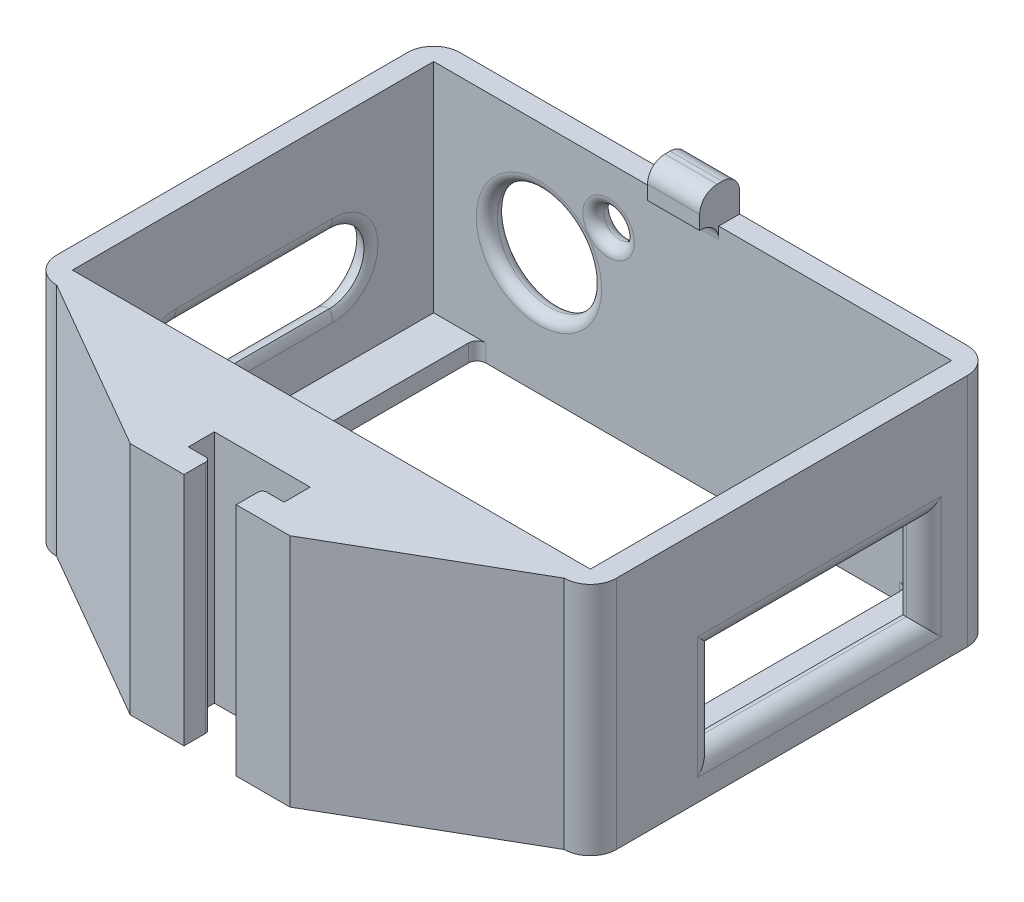
SolidWorks part; units mm, degrees
ref_plane "Спереди" through (0, 0, 0) normal (0, 0, 1) x (1, 0, 0)
ref_plane "Сверху" through (0, 0, 0) normal (0, 1, 0) x (1, 0, 0)
ref_plane "Справа" through (0, 0, 0) normal (1, 0, 0) x (0, 0, -1)
other "Configuration Table"
sketch "Эскиз1" plane through (0, 0, 0) normal (0, 1, 0) x (1, 0, 0)
  line L0 (-2.4, 43.9) -> (61.9, 43.9)
  line L1 (0, 0) -> (59.5, 0)
  line L2 (0, 0) -> (0, 41.5)
  line L3 (0, 41.5) -> (59.5, 41.5)
  line L4 (59.5, 0) -> (59.5, 41.5)
  line L5 (61.9, -2.4) -> (61.9, 43.9)
  line L6 (-2.4, -2.4) -> (61.9, -2.4)
  line L7 (-2.4, -2.4) -> (-2.4, 43.9)
  line L12 (5, 41.5) -> (5, 0)
  line L16 (54.5, 41.5) -> (54.5, 0)
  dimension "D1" = 59.5
  dimension "D2" = 41.5
  dimension "D4" = 5
  dimension "D5" = 5
  dimension "D6" = 41.5
  dimension "D7" = 41.5
  dimension "D3" = 2.4
extrude "Бобышка-Вытянуть2" add sketch "Эскиз1" along normal blind 27 contours L7 L6 L5 L0 L4 L1 L2 L3 region at (29.75, 0, -43.1077)
extrude "Бобышка-Вытянуть3" add sketch "Эскиз1<3>" along normal blind 2 contours L12 L3 L2 L1 | L3 L16 L1 L4 region at (2.5, 0, -20.75) region at (57, 0, -20.75)
sketch "Эскиз1<3>" plane through (0, 0, 0) normal (0, 1, 0) x (1, 0, 0) same geometry as "Эскиз1"
fillet "Скругление1" radius 3 4 edges at (-2.4, 13.5, -43.9) (61.9, 13.5, -43.9) (61.9, 13.5, 2.4) (-2.4, 13.5, 2.4)
fillet "Скругление2" radius 1 4 edges at (54.5, 1, 0) (5, 1, 0) (5, 1, -41.5) (54.5, 1, -41.5)
sketch "Эскиз2" plane through (0, 0, -43.9) normal (0, 0, -1) x (-1, 0, 0)
  line L0 (2.4, 27) -> (2.4, 0) construction
  line L4 (-58.9, 0) -> (-0.6, 0)
  line L5 (-0.6, 0) -> (-0.6, 27)
  line L6 (-0.6, 27) -> (-58.9, 27)
  line L7 (-58.9, 27) -> (-58.9, 0)
  line L8 (-58.9, 0) -> (-0.6, 0)
  line L9 (-0.6, 0) -> (-0.6, 27)
  line L10 (-0.6, 27) -> (-58.9, 27)
  line L11 (-58.9, 27) -> (-58.9, 0)
  circle A0 centre (-12.1, 14) radius 6
  circle A1 centre (-20.1, 20.5) radius 1.75
  dimension "D1" = 0
  dimension "D3" = 12
  dimension "D5" = 22.5
  dimension "D6" = 3.5
  dimension "D2" = 14.5
  dimension "D4" = 13
  dimension "D7" = 6.5
extrude "Вырез-Вытянуть2" cut sketch "Эскиз2" against normal blind 8 contours A0 | A1
sketch "Эскиз4" plane through (61.9, 0, 0) normal (1, 0, 0) x (0, 0, -1)
  line L0 (43.9, 27) -> (43.9, 0) construction
  line L1 (11.9, 14.5) -> (35.9, 14.5)
  line L2 (11.9, 14.5) -> (11.9, 4.5)
  line L3 (11.9, 4.5) -> (35.9, 4.5)
  line L4 (0.6, 0) -> (40.9, 0)
  line L5 (40.9, 0) -> (40.9, 27)
  line L6 (40.9, 27) -> (0.6, 27)
  line L7 (0.6, 27) -> (0.6, 0)
  line L8 (0.6, 0) -> (40.9, 0)
  line L9 (40.9, 0) -> (40.9, 27)
  line L10 (40.9, 27) -> (0.6, 27)
  line L11 (0.6, 27) -> (0.6, 0)
  line L12 (35.9, 14.5) -> (35.9, 4.5)
  dimension "D2" = 10
  dimension "D3" = 24
  dimension "D4" = 8
  dimension "D5" = 4.5
  dimension "D1" = 0
extrude "Вырез-Вытянуть4" cut sketch "Эскиз4" against normal blind 12 contours L2 L3 L12 L1
fillet "Скругление5" radius 2 4 edges at (61.9, 4.5, -23.9) (61.9, 9.5, -35.9) (61.9, 9.5, -11.9) (61.9, 14.5, -23.9)
sketch "Эскиз10" plane through (-2.4, 0, 0) normal (-1, 0, 0) x (0, 0, 1)
  line L0 (-29.9, 12) -> (-11.9, 12) construction
  line L1 (-29.9, 16) -> (-11.9, 16)
  line L2 (-29.9, 8) -> (-11.9, 8)
  line L3 (-0.6, 0) -> (-40.9, 0) construction
  line L5 (-43.9, 0) -> (-43.9, 27) construction
  arc A0 (-29.9, 16) -> (-29.9, 8) centre (-29.9, 12) ccw
  arc A1 (-11.9, 8) -> (-11.9, 16) centre (-11.9, 12) ccw
  point P2 (-20.9, 12)
  dimension "D3" = 8
  dimension "D1" = 18
  dimension "D2" = 8
  dimension "D4" = 23
extrude "Вырез-Вытянуть5" cut sketch "Эскиз10" against normal blind 12 contours L1 A1 L2 A0
fillet "Скругление6" radius 2 4 edges at (-2.4, 8, -20.9) (-2.4, 12, -33.9) (-2.4, 16, -20.9) (-2.4, 12, -7.9)
fillet "Скругление7" radius 2 4 edges at (0, 8, -20.9) (0, 12, -33.9) (0, 16, -20.9) (0, 12, -7.9)
fillet "Скругление16" radius 1.2 4 edges at (18.35, 20.5, -41.5) (18.35, 20.5, -43.9) (6.1, 14, -41.5) (6.1, 14, -43.9)
ref_plane "Плоскость1" through (29.75, 0, 0) normal (1, 0, 0) x (0, 0, -1)
sketch "Эскиз16" plane through (29.75, 0, 0) normal (1, 0, 0) x (0, 0, -1)
  line L0 (43.9, 29.2618) -> (43.9, 24.6269)
  line L2 (43.9, 27) -> (43.9, 29.2618)
  line L3 (41.9, 31.2618) -> (41.3153, 31.2618)
  line L4 (43.9, 27) -> (40.9, 27)
  line L5 (43.9, 0) -> (43.9, 27)
  line L6 (40.9, 0) -> (43.9, 0)
  line L7 (40.9, 27) -> (40.9, 0)
  line L9 (43.9, 0) -> (43.9, 27)
  line L10 (40.9, 0) -> (43.9, 0)
  line L12 (0, 27) -> (0, 2)
  line L13 (0, 2) -> (41.5, 2)
  line L14 (41.5, 2) -> (41.5, 27)
  line L15 (41.5, 27) -> (0, 27)
  line L16 (0, 27) -> (0, 2)
  line L17 (0, 2) -> (41.5, 2)
  line L20 (39.3153, 29.2618) -> (39.3153, 27.6498)
  line L21 (39.3153, 27.6498) -> (39.5, 27.6498)
  line L22 (41.5, 25.6498) -> (41.5, 24.6269)
  line L23 (41.5, 24.6269) -> (43.9, 24.6269)
  arc A0 (41.9, 31.2618) -> (43.9, 29.2618) centre (41.9, 29.2618) cw
  arc A1 (41.3153, 31.2618) -> (39.3153, 29.2618) centre (41.3153, 29.2618) ccw
  arc A2 (41.5, 25.6498) -> (39.5, 27.6498) centre (39.5, 25.6498) ccw
  dimension "D2" = 0
  dimension "D3" = 2
  dimension "D1" = 0
extrude "Бобышка-Вытянуть9" add sketch "Эскиз16" along normal mid plane 6 contours A0 L3 A1 L20 L21 A2 L22 L23 L0
sketch "Эскиз17" plane through (0, 27, 0) normal (0, 1, 0) x (1, 0, 0)
  line L0 (0.6, -2.4) -> (58.9, -2.4) construction
  line L1 (0.6, -2.4) -> (58.9, -2.4)
  line L2 (0.6, -2.4) -> (20.5772, -13.9338)
  line L3 (54.9, -2.4) -> (38.3869, -11.9338)
  line L4 (4.6, -2.4) -> (21.1131, -11.9338)
  line L5 (29.75, -2.4) -> (29.75, -13.9338)
  line L6 (8.0641, -4.4) -> (30.7742, -17.5117) construction
  line L7 (8.0641, -4.4) -> (58.9, -4.4) construction
  line L8 (58.9, -2.4) -> (38.9228, -13.9338)
  line L9 (29.75, -13.9338) -> (20.5772, -13.9338)
  line L10 (29.75, -11.9338) -> (21.1131, -11.9338)
  line L11 (42.4354, -13.9338) -> (17.1131, -13.9338) construction
  line L12 (0.6, -2.4) -> (29.7742, -19.2437) construction
  line L13 (42.4354, -11.9338) -> (17.1131, -11.9338) construction
  line L14 (29.75, -11.9338) -> (38.3869, -11.9338)
  line L15 (29.75, -13.9338) -> (38.9228, -13.9338)
  line L16 (-2.4, 0.6) -> (-2.4, 40.9) construction
  point P25 (38.3869, -11.9338)
  point P28 (21.1131, -11.9338)
  line M26 (0.6, -2.4) -> (58.9, -2.4)
  dimension "D1" = 30
  dimension "D4" = 2
  dimension "D2" = 2
extrude "Бобышка-Вытянуть11" add sketch "Эскиз17" against normal up to vertex (27 mm away) contours L5 L14 L3 M26 | L10 L5 L1 L4 | L5 L15 L8 L1 L3 L14 | L5 L10 L4 L2 L9 M26 region at (15.7301, 27, 9.2458) region at (20.6307, 27, 6.3903) region at (38.8693, 27, 6.3903) region at (43.7699, 27, 9.2458) up to point (58.9, 0, 2.4)
sketch "Эскиз19" plane through (0, 27, 0) normal (0, 1, 0) x (1, 0, 0)
  line L0 (20.5772, -13.9338) -> (38.9228, -13.9338) construction
  line L1 (0, 0) -> (59.5, 0) construction
  line L2 (20.5772, -13.9338) -> (38.9228, -13.9338) construction
  line L3 (0, 0) -> (59.5, 0)
  line L4 (29.75, 0) -> (29.75, -13.9338) construction
  line L5 (26.75, -13.9338) -> (32.75, -13.9338)
  line L6 (32.75, -13.9338) -> (32.75, -10.9338)
  line L7 (32.75, -10.9338) -> (35.25, -10.9338)
  line L8 (35.25, -10.9338) -> (35.25, -7.9338)
  line L9 (35.25, -7.9338) -> (24.25, -7.9338)
  line L10 (29.75, -7.9338) -> (29.75, -13.9338)
  line L11 (24.25, -10.9338) -> (24.25, -7.9338)
  line L12 (26.75, -10.9338) -> (24.25, -10.9338)
  line L13 (26.75, -13.9338) -> (26.75, -10.9338)
  line M24 (20.5772, -13.9338) -> (38.9228, -13.9338)
  dimension "D1" = 3
  dimension "D2" = 3
  dimension "D3" = 3
  dimension "D4" = 2.5
extrude "Вырез-Вытянуть6" cut sketch "Эскиз19" against normal through all contours L13 L10 L9 L11 L12 M24 | L9 L10 L5 L6 L7 L8 region at (27.4412, 27, 10.4927) region at (32.0588, 27, 10.4927)
fillet "Скругление17" radius 0.5 2 edges at (32.75, 13.5, 10.9338) (26.75, 13.5, 10.9338)
